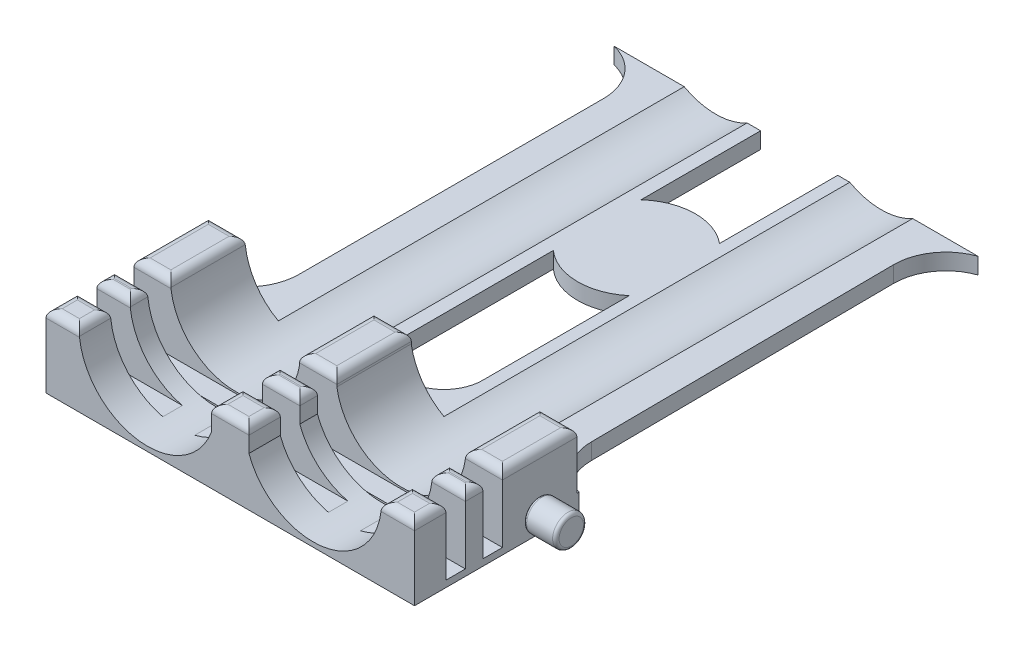
SolidWorks part; units mm, degrees
ref_plane "Front Plane" through (0, 0, 0) normal (0, 0, 1) x (1, 0, 0)
ref_plane "Top Plane" through (0, 0, 0) normal (0, 1, 0) x (1, 0, 0)
ref_plane "Right Plane" through (0, 0, 0) normal (1, 0, 0) x (0, 0, -1)
sketch "Sketch1" plane through (0, 0, 0) normal (0, 1, 0) x (1, 0, 0)
  line L1 (-12.5, -45) -> (12.5, -45)
  line L2 (-12.5, -45) -> (-12.5, 45)
  line L3 (-12.5, 45) -> (12.5, 45)
  line L4 (12.5, -45) -> (12.5, 45)
  line L5 (-12.5, -45) -> (12.5, 45) construction
  line L6 (-12.5, 45) -> (12.5, -45) construction
  point P0 (0, 0)
  dimension "D1" = 90
  dimension "D2" = 25
extrude "Boss-Extrude1" add sketch "Sketch1" along normal blind 9
sketch "Sketch4" plane through (0, 9, 0) normal (0, 1, 0) x (1, 0, 0)
  line L0 (0, 36.8) -> (0, -45) construction
  line L1 (0, 45) -> (0, -45) construction
  line L2 (-12.5, -45) -> (12.5, -45) construction
  line L3 (12.5, 45) -> (-12.5, 45) construction
  line L4 (0, 36.8) -> (-8, 36.8)
  line L5 (0, 36.8) -> (0, -34.2)
  line L6 (0, -34.2) -> (-8, -34.2)
  line L7 (-8, 36.8) -> (-8, -34.2)
  line L8 (0, 36.8) -> (-8, -34.2) construction
  line L9 (0, -34.2) -> (-8, 36.8) construction
  line L10 (-12.5, 0) -> (12.5, 0) construction
  line L11 (-12.5, 45) -> (-12.5, -45) construction
  line L12 (12.5, -45) -> (12.5, 45) construction
  point P9 (-4, 1.3)
  dimension "D1" = 71
  dimension "D2" = 8
revolve "Syringe Body slot" cut sketch "Sketch4" angle 360 about L5
sketch "Sketch5" plane through (0, 9, 0) normal (0, 1, 0) x (1, 0, 0)
  line L0 (-13.75, -35.3671) -> (13.75, -35.3671) construction
  line L1 (8, -34.2) -> (-8, -34.2) construction
  line L2 (-12.5, 45) -> (-12.5, -45) construction
  line L3 (0, -34.2) -> (0, -35.3671) construction
  line L4 (12.5, -45) -> (12.5, 45) construction
  line L5 (-12.5, -36.5671) -> (12.5, -36.5671)
  line L6 (-12.5, -36.5671) -> (-12.5, -34.1671)
  line L7 (-12.5, -34.1671) -> (12.5, -34.1671)
  line L8 (12.5, -36.5671) -> (12.5, -34.1671)
  line L9 (-12.5, -36.5671) -> (12.5, -34.1671) construction
  line L10 (-12.5, -34.1671) -> (12.5, -36.5671) construction
  line L11 (-13.75, -39.9361) -> (13.75, -39.9361) construction
  line L12 (0, -38.7691) -> (0, -39.9361) construction
  line L13 (-14, -41.1361) -> (14, -41.1361)
  line L14 (-14, -41.1361) -> (-14, -38.7361)
  line L15 (-14, -38.7361) -> (14, -38.7361)
  line L16 (14, -41.1361) -> (14, -38.7361)
  line L17 (-14, -41.1361) -> (14, -38.7361) construction
  line L18 (-14, -38.7361) -> (14, -41.1361) construction
  point P6 (0, -35.3671)
  point P20 (0, -39.9361)
  dimension "D2" = 13.75
extrude "Flange Slot" cut sketch "Sketch5" against normal blind 8.2
sketch "Sketch6" plane through (0, 9, 0) normal (0, 1, 0) x (1, 0, 0)
  line L0 (0, -36.5671) -> (0, -45) construction
  line L1 (-12.5, -36.5671) -> (12.5, -36.5671) construction
  line L2 (-12.5, -45) -> (12.5, -45) construction
  line L4 (0, -45) -> (-8.4329, -45)
  line L5 (0, -45) -> (0, -36.5671)
  line L6 (0, -36.5671) -> (-8.4329, -36.5671)
  line L7 (-8.4329, -45) -> (-8.4329, -36.5671)
  line L8 (0, -45) -> (-8.4329, -36.5671) construction
  line L9 (0, -36.5671) -> (-8.4329, -45) construction
  point P9 (-4.2165, -40.7835)
revolve "Plunger Slot" cut sketch "Sketch6" angle 360 about L5
sketch "Sketch18" plane through (0, 9, 0) normal (0, 1, 0) x (1, 0, 0)
  line L1 (-12.5, -25) -> (12.5, -25)
  line L2 (-12.5, -25) -> (-12.5, 25)
  line L3 (-12.5, 25) -> (12.5, 25)
  line L4 (12.5, -25) -> (12.5, 25)
  line L5 (-12.5, -25) -> (12.5, 25) construction
  line L6 (-12.5, 25) -> (12.5, -25) construction
  point P0 (0, 0)
  dimension "D1" = 50
  dimension "D2" = 25
extrude "Syringe Bay" cut sketch "Sketch18" against normal blind 7
sketch "Sketch26" plane through (0, 9, 0) normal (0, 1, 0) x (1, 0, 0)
  line L0 (12.5, 25) -> (8, 25) construction
  line L1 (-19.8999, 25) -> (18.4526, 25)
  line L2 (-19.8999, 25) -> (-19.8999, 45.2156)
  line L3 (-19.8999, 45.2156) -> (18.4526, 45.2156)
  line L4 (18.4526, 25) -> (18.4526, 45.2156)
extrude "Cut-Extrude14" cut sketch "Sketch26" against normal blind 10
pattern_linear "LPattern3" count 2 spacing 20.4 along (1, 0, 0) of bodies 163
sketch "Sketch31" plane through (-12.5, 0, 0) normal (-1, 0, 0) x (0, 0, 1)
  line L0 (25, 9) -> (34.1671, 9) construction
  circle A0 centre (29.6873, 2.2313) radius 1.9
  dimension "D1" = 1.9
extrude "Cut-Extrude16" cut sketch "Sketch31" against normal blind 4
sketch "Sketch33" plane through (32.9, 0, 0) normal (1, 0, 0) x (0, 0, -1)
  circle A0 centre (-29.6873, 2.2313) radius 1.9
  dimension "D1" = 1.9
extrude "Boss-Extrude2" add sketch "Sketch33" along normal blind 4
fillet "Fillet1" radius 0.4 2 edges at (36.9, 2.2313, 27.7873) (32.9, 2.2313, 27.7873)
fillet "Fillet2" radius 0.6 2 edges at (-12.5, 2.2313, 31.5873) (-8.5, 2.2313, 31.5873)
sketch "Sketch35" plane through (0, 2, 0) normal (0, 1, 0) x (1, 0, 0)
  line L0 (-14, 25) -> (-14, -25) construction
  line L1 (-14, 0) -> (-14, -25) construction
  line L2 (-14, -12.5) -> (-14, 12.5) construction
  line L3 (-14, -12.5) -> (-14, -25) construction
  line L4 (-14, -25) -> (-14, -18.75) construction
  line L5 (-14, 25) -> (-14, 12.5) construction
  line L6 (-14, 18.75) -> (-14, -18.75) construction
  line L7 (-14, 18.75) -> (-14, -18.75) construction
  line L8 (-7.5725, 18.75) -> (-7.5725, -18.75)
  line L9 (-20.4275, 18.75) -> (-20.4275, -18.75)
  line L10 (10.2, 25) -> (10.4665, -45) construction
  line L12 (-12.5, 25) -> (32.9, 25) construction
  line L15 (8.4329, -45) -> (12.5, -45) construction
  line L18 (34.4469, 18.9344) -> (34.7324, -18.5645) construction
  line L23 (9.6592, -17.7945) -> (10.288, -2.3812) construction
  line L24 (10.288, 25.2845) -> (10.288, 12.1282) construction
  line L25 (10.288, 25.2845) -> (10.288, 12.1282) construction
  line L26 (15.038, 25.2845) -> (15.038, 10.4351)
  line L27 (5.538, 25.2845) -> (5.538, 10.2777)
  line L28 (-14, 0) -> (2.8875, 0) construction
  line L29 (9.6592, 0) -> (14.4092, 0) construction
  line L30 (28.0196, 18.8855) -> (28.3051, -18.6134)
  line L31 (10.288, -2.3812) -> (10.288, -18.75) construction
  line L32 (10.288, -2.3812) -> (10.288, -18.75) construction
  line L33 (40.8742, 18.9834) -> (41.1597, -18.5156)
  line L34 (15.038, -0.688) -> (15.038, -18.75)
  line L35 (5.538, -0.5306) -> (5.538, -18.75)
  line L36 (10.2, 25) -> (10.2, -35.6686) construction
  line L37 (34.4469, 18.9344) -> (34.7324, -18.5645) construction
  line L38 (34.3993, 25.1842) -> (34.4945, 12.6846) construction
  line L39 (34.78, -24.8143) -> (34.7324, -18.5645) construction
  line L40 (34.6848, -12.3147) -> (34.78, -24.8143) construction
  line L41 (34.6848, -12.3147) -> (34.4945, 12.6846) construction
  line L42 (34.5896, 0.185) -> (34.78, -24.8143) construction
  line L43 (34.3993, 25.1842) -> (34.78, -24.8143) construction
  arc A0 (-7.5725, 18.75) -> (-20.4275, 18.75) centre (-14, 18.75) ccw
  arc A1 (-20.4275, -18.75) -> (-7.5725, -18.75) centre (-14, -18.75) ccw
  arc A4 (15.038, 25.2845) -> (5.538, 25.2845) centre (10.288, 25.2845) ccw
  arc A5 (5.538, -18.75) -> (15.038, -18.75) centre (10.288, -18.75) ccw
  arc A6 (5.538, -0.5306) -> (15.038, -0.688) centre (10.3789, 4.8735) ccw
  arc A7 (15.038, 10.4351) -> (5.538, 10.2777) centre (10.3789, 4.8735) ccw
  arc A8 (28.0196, 18.8855) -> (40.8742, 18.9834) centre (34.4469, 18.9344) cw
  arc A9 (41.1597, -18.5156) -> (28.3051, -18.6134) centre (34.7324, -18.5645) cw
  point P9 (-14, 0)
  point P21 (34.5896, 0.185)
  point P36 (9.6592, 0)
  dimension "D1" = 25
extrude "Cut-Extrude17" cut sketch "Sketch35" against normal blind 10
combine bodies "Combine2" operation type add bodies to combine 176 175 175 169
sketch "Sketch36" plane through (0, 2, 0) normal (0, 1, 0) x (1, 0, 0)
  circle A0 centre (10.3789, 4.8735) radius 3
  dimension "D1" = 3
extrude "Boss-Extrude3" [suppressed] add sketch "Sketch36" along normal blind 35
fillet "Fillet5" [suppressed] radius 2
fillet "Fillet7" radius 1 36 edges at (7.9, 9, 29.5835) (10.2, 9, 25) (30.65, 9, 25) (10.2, 9, 45) (32.9, 9, 37.6516) (32.9, 9, 29.5835) (7.9, 9, 37.6516) (7.9, 9, 43.0681) (10.2, 9, 41.1361) (30.8665, 9, 38.7361) (-10.25, 9, 34.1671) (12.5, 9, 37.6516) (12.5, 9, 43.0681) (-8.4329, 9, 37.6516) (-8.4329, 9, 43.0681) (-12.5, 9, 29.5835) (-8, 9, 29.5835) (12.5, 9, 29.5835) (-12.5, 9, 37.6516) (-12.5, 9, 43.0681) (-10.4665, 9, 45) (-10.4665, 9, 38.7361) (-10.4665, 9, 36.5671) (-10.4665, 9, 41.1361) (-10.25, 9, 25) (10.2, 9, 34.1671) (10.2, 9, 36.5671) (30.65, 9, 34.1671) (32.9, 9, 43.0681) (10.2, 9, 38.7361) (30.8665, 9, 41.1361) (30.8665, 9, 36.5671) (30.8665, 9, 45) (28.8329, 9, 37.6516) (28.8329, 9, 43.0681) (28.4, 9, 29.5835)
